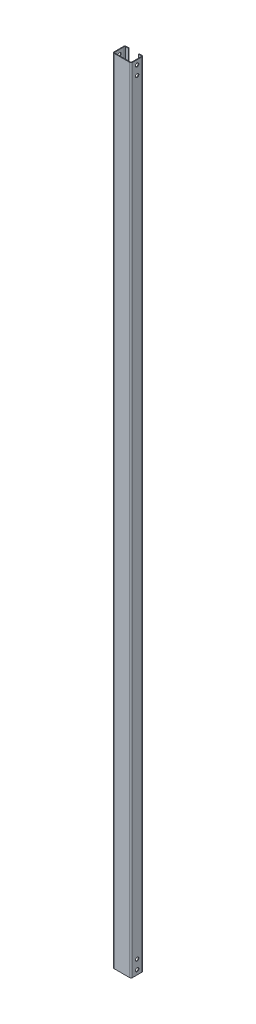
SolidWorks part; units mm, degrees
note: The reader was unsure of these and kept them because the rebuilt part matched: flange length of "Edge-Flange1", "Edge-Flange2".
material "AISI 304"
ref_plane "Front Plane" through (0, 0, 0) normal (0, 0, 1) x (1, 0, 0)
ref_plane "Top Plane" through (0, 0, 0) normal (0, 1, 0) x (1, 0, 0)
ref_plane "Right Plane" through (0, 0, 0) normal (1, 0, 0) x (0, 0, -1)
sketch "Sketch1" plane through (0, 0, 0) normal (0, 0, 1) x (1, 0, 0)
  line L1 (-30, 1300) -> (30, 1300)
  line L2 (-30, 1300) -> (-30, -1300)
  line L3 (-30, -1300) -> (30, -1300)
  line L4 (30, 1300) -> (30, -1300)
  line L5 (-30, 1300) -> (30, -1300) construction
  line L6 (-30, -1300) -> (30, 1300) construction
  point P0 (0, 0)
  dimension "D1" = 2600
  dimension "D2" = 60
base flange "Base-Flange1" sketch "Sketch1" thickness 2 reverse thickness direction no parameters "D1"=2.5
edge flange "Edge-Flange1" sketch "Sketch10" flange profiles "Sketch10", "Sketch11" flange angle 90 flange length 40 flange position material inside bend radius 2.5 thickness 2 relief obround parameters "D6"=10, "D8"=1
sketch "Sketch10" plane through (30, 0, -2) normal (-1, 0, 0) x (0, 1, 0)
  line L2 (1300, 0) -> (1300, 38)
  line L3 (1300, 38) -> (-1300, 38)
  line L4 (-1300, 38) -> (-1300, 0)
  line L5 (-1300, 0) -> (1300, 0) construction
  line L6 (-1300, 0) -> (1300, 0)
sketch "Sketch11" plane through (-30, 0, -2) normal (1, 0, 0) x (0, -1, 0)
  line L2 (1300, 0) -> (1300, 38)
  line L3 (1300, 38) -> (-1300, 38)
  line L4 (-1300, 38) -> (-1300, 0)
  line L5 (-1300, 0) -> (1300, 0) construction
  line L6 (-1300, 0) -> (1300, 0)
bend "EdgeBend1" bend radius 2.5 bend angle 90 parameters "D5"=1
bend "EdgeBend2" bend radius 2.5 bend angle 90 parameters "D5"=2
edge flange "Edge-Flange2" sketch "Sketch16" flange profiles "Sketch16", "Sketch17" flange angle 90 flange length 13 flange position material inside bend radius 2.5 thickness 2 relief obround parameters "D6"=10, "D8"=1
sketch "Sketch16" plane through (28, 0, -40) normal (0, 0, -1) x (0, -1, 0)
  line L2 (1300, 0) -> (1300, 11)
  line L3 (1300, 11) -> (-1300, 11)
  line L4 (-1300, 11) -> (-1300, 0)
  line L7 (1300, 0) -> (-1300, 0) construction
  line L8 (1300, 0) -> (-1300, 0)
sketch "Sketch17" plane through (-28, 0, -40) normal (0, 0, -1) x (0, 1, 0)
  line L2 (1300, 0) -> (1300, 11)
  line L3 (1300, 11) -> (-1300, 11)
  line L4 (-1300, 11) -> (-1300, 0)
  line L7 (1300, 0) -> (-1300, 0) construction
  line L8 (1300, 0) -> (-1300, 0)
bend "EdgeBend3" bend radius 2.5 bend angle 90 parameters "D5"=3
bend "EdgeBend4" bend radius 2.5 bend angle 90 parameters "D5"=4
sketch "Sketch18" plane through (30, 0, 0) normal (1, 0, 0) x (0, 0, -1)
  line L0 (4.5, 1300) -> (35.5, 1300) construction
  line L2 (4.5, 1300) -> (35.5, 1300) construction
  circle A0 centre (20, 1255) radius 5.5
  circle A1 centre (20, 1285) radius 5.5
  point P4 (20, 1300)
  dimension "D1" = 11
  dimension "D2" = 30
  dimension "D3" = 15
  dimension "D4" = 0
extrude "Cut-Extrude1" cut sketch "Sketch18" against normal through all and the other way through all normal cut yes
mirror "Mirror1" about plane through (0, 0, 0) normal (0, 1, 0) of "Cut-Extrude1"
sketch "Bend-Lines1" [suppressed] plane through (0, 0, 0) normal (0, 1, 0) x (1, 0, 0)
sketch "Bounding-Box1" [suppressed] plane through (0, 0, 0) normal (0, 1, 0) x (1, 0, 0)
sheet metal parameters "Sheet-Metal1" thickness 2 parameters "D1"=2.5
flat pattern "Flat-Pattern1" [suppressed]
sketch "Bend-Lines2" plane through (0, 0, 0) normal (0, 1, 0) x (1, 0, 0)
sketch3d "Bounding-Box2" [suppressed]
  line L0 (-20, 1400, 0) -> (-20, -1400, 0) construction
  line L1 (20, 1400, 0) -> (20, -1400, 0) construction
  line L2 (-20, 1400, 0) -> (20, 1400, 0) construction
  line L3 (-20, -1400, 0) -> (20, -1400, 0) construction
sheet metal parameters "Sheet-Metal2" thickness 2 parameters "D1"=2.5
flat pattern "Flat-Pattern1"
sketch "Bend-Lines2" plane through (0, 0, 0) normal (0, 0, 1) x (1, 0, 0)
  line L0 (-18.0918, 1400) -> (-18.0918, -1400) construction
  line L1 (18.0918, -1400) -> (18.0918, 1400) construction
  line L2 (-18.0918, 1400) -> (-18.0918, -1400) construction
  line L3 (18.0918, -1400) -> (18.0918, 1400) construction
sketch3d "Bounding-Box2" [suppressed]
  line L0 (46.1836, 1400, 0) -> (46.1836, -1400, 0) construction
  line L1 (-46.1836, 1400, 0) -> (-46.1836, -1400, 0) construction
  line L2 (46.1836, 1400, 0) -> (-46.1836, 1400, 0) construction
  line L3 (46.1836, -1400, 0) -> (-46.1836, -1400, 0) construction
bend of the flat pattern "Flatten-<EdgeBend1>1"
bend of the flat pattern "Flatten-<EdgeBend2>1"
sheet metal parameters "Sheet-Metal3" thickness 2 parameters "D1"=2.5
flat pattern "Flat-Pattern1"
sketch "Bend-Lines2" plane through (0, 0, 0) normal (0, 0, 1) x (1, 0, 0)
  line L0 (-28.0918, 1300) -> (-28.0918, -1300) construction
  line L1 (28.0918, -1300) -> (28.0918, 1300) construction
  line L2 (-28.0918, 1300) -> (-28.0918, -1300) construction
  line L3 (28.0918, -1300) -> (28.0918, 1300) construction
  line L4 (-64.2754, 1300) -> (-64.2754, -1300) construction
  line L5 (64.2754, -1300) -> (64.2754, 1300) construction
  line L6 (-64.2754, 1300) -> (-64.2754, -1300) construction
  line L7 (64.2754, -1300) -> (64.2754, 1300) construction
sketch3d "Bounding-Box2" [suppressed]
  line L0 (75.3673, 1300, 0) -> (75.3673, -1300, 0) construction
  line L1 (-75.3673, 1300, 0) -> (-75.3673, -1300, 0) construction
  line L2 (75.3673, 1300, 0) -> (-75.3673, 1300, 0) construction
  line L3 (75.3673, -1300, 0) -> (-75.3673, -1300, 0) construction
bend of the flat pattern "Flatten-<EdgeBend1>1"
bend of the flat pattern "Flatten-<EdgeBend2>1"
bend of the flat pattern "Flatten-<EdgeBend3>1"
bend of the flat pattern "Flatten-<EdgeBend4>1"
sheet metal parameters "Sheet-Metal4" thickness 2 parameters "D1"=2.5
flat pattern "Flat-Pattern1"
sketch "Bend-Lines2" plane through (0, 0, 0) normal (0, 0, 1) x (1, 0, 0)
  line L0 (-18.0918, 1400) -> (-18.0918, -1400) construction
  line L1 (18.0918, -1400) -> (18.0918, 1400) construction
  line L2 (-18.0918, 1400) -> (-18.0918, -1400) construction
  line L3 (18.0918, -1400) -> (18.0918, 1400) construction
  line L4 (-44.2754, 1400) -> (-44.2754, -1400) construction
  line L5 (44.2754, -1400) -> (44.2754, 1400) construction
  line L6 (-44.2754, 1400) -> (-44.2754, -1400) construction
  line L7 (44.2754, -1400) -> (44.2754, 1400) construction
sketch3d "Bounding-Box2" [suppressed]
  line L0 (57.3673, 1400, 0) -> (57.3673, -1400, 0) construction
  line L1 (-57.3673, 1400, 0) -> (-57.3673, -1400, 0) construction
  line L2 (57.3673, 1400, 0) -> (-57.3673, 1400, 0) construction
  line L3 (57.3673, -1400, 0) -> (-57.3673, -1400, 0) construction
bend of the flat pattern "Flatten-<EdgeBend1>1"
bend of the flat pattern "Flatten-<EdgeBend2>1"
bend of the flat pattern "Flatten-<EdgeBend3>1"
bend of the flat pattern "Flatten-<EdgeBend4>1"
sheet metal parameters "Sheet-Metal5" thickness 2 parameters "D1"=2.5
flat pattern "Flat-Pattern1"
sketch "Bend-Lines2" plane through (0, 0, 0) normal (0, 0, 1) x (1, 0, 0)
  line L0 (-28.0918, 1300) -> (-28.0918, -1300) construction
  line L1 (28.0918, -1300) -> (28.0918, 1300) construction
  line L2 (-28.0918, 1300) -> (-28.0918, -1300) construction
  line L3 (28.0918, -1300) -> (28.0918, 1300) construction
  line L4 (-64.2754, 1300) -> (-64.2754, -1300) construction
  line L5 (64.2754, -1300) -> (64.2754, 1300) construction
  line L6 (-64.2754, 1300) -> (-64.2754, -1300) construction
  line L7 (64.2754, -1300) -> (64.2754, 1300) construction
sketch3d "Bounding-Box2" [suppressed]
  line L0 (75.3673, 1300, 0) -> (75.3673, -1300, 0) construction
  line L1 (-75.3673, 1300, 0) -> (-75.3673, -1300, 0) construction
  line L2 (75.3673, 1300, 0) -> (-75.3673, 1300, 0) construction
  line L3 (75.3673, -1300, 0) -> (-75.3673, -1300, 0) construction
bend of the flat pattern "Flatten-<EdgeBend1>1"
bend of the flat pattern "Flatten-<EdgeBend2>1"
bend of the flat pattern "Flatten-<EdgeBend3>1"
bend of the flat pattern "Flatten-<EdgeBend4>1"
